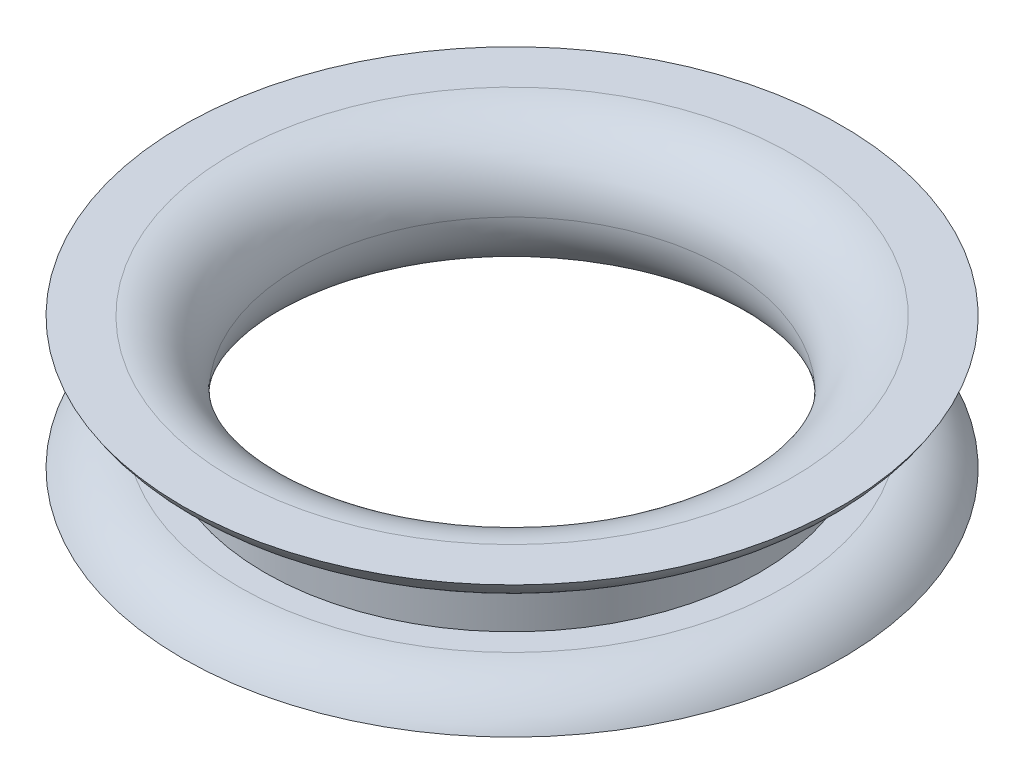
SolidWorks part; units mm, degrees
ref_plane "Front Plane" through (0, 0, 0) normal (0, 0, 1) x (1, 0, 0)
ref_plane "Top Plane" through (0, 0, 0) normal (0, 1, 0) x (1, 0, 0)
ref_plane "Right Plane" through (0, 0, 0) normal (1, 0, 0) x (0, 0, -1)
sketch "Sketch1" plane through (0, 0, 0) normal (0, 1, 0) x (1, 0, 0)
  circle A0 centre (0, 0) radius 12.7
  dimension "D1" = 25.4
extrude "Boss-Extrude1" add sketch "Sketch1" along normal blind 1.27
sketch "Sketch2" plane through (0, 1.27, 0) normal (0, 1, 0) x (1, 0, 0)
  circle A0 centre (0, 0) radius 9.525
  dimension "D1" = 19.05
extrude "Boss-Extrude2" add sketch "Sketch2" along normal blind 2.54
sketch "Sketch3" plane through (0, 3.81, 0) normal (0, 1, 0) x (1, 0, 0)
  circle A0 centre (0, 0) radius 12.7
  dimension "D1" = 25.4
extrude "Boss-Extrude3" add sketch "Sketch3" along normal blind 1.27
shell "Shell1" thickness 1.27 removed face at (0, 5.08, 12.7) removed face at (0, 0, 12.7)
fillet "Fillet1" radius 2.54 2 edges at (0, 1.27, 12.7) (0, 3.81, 12.7)
fillet "Fillet2" radius 2.54 2 edges at (0, 0, 8.255) (0, 5.08, 8.255)
